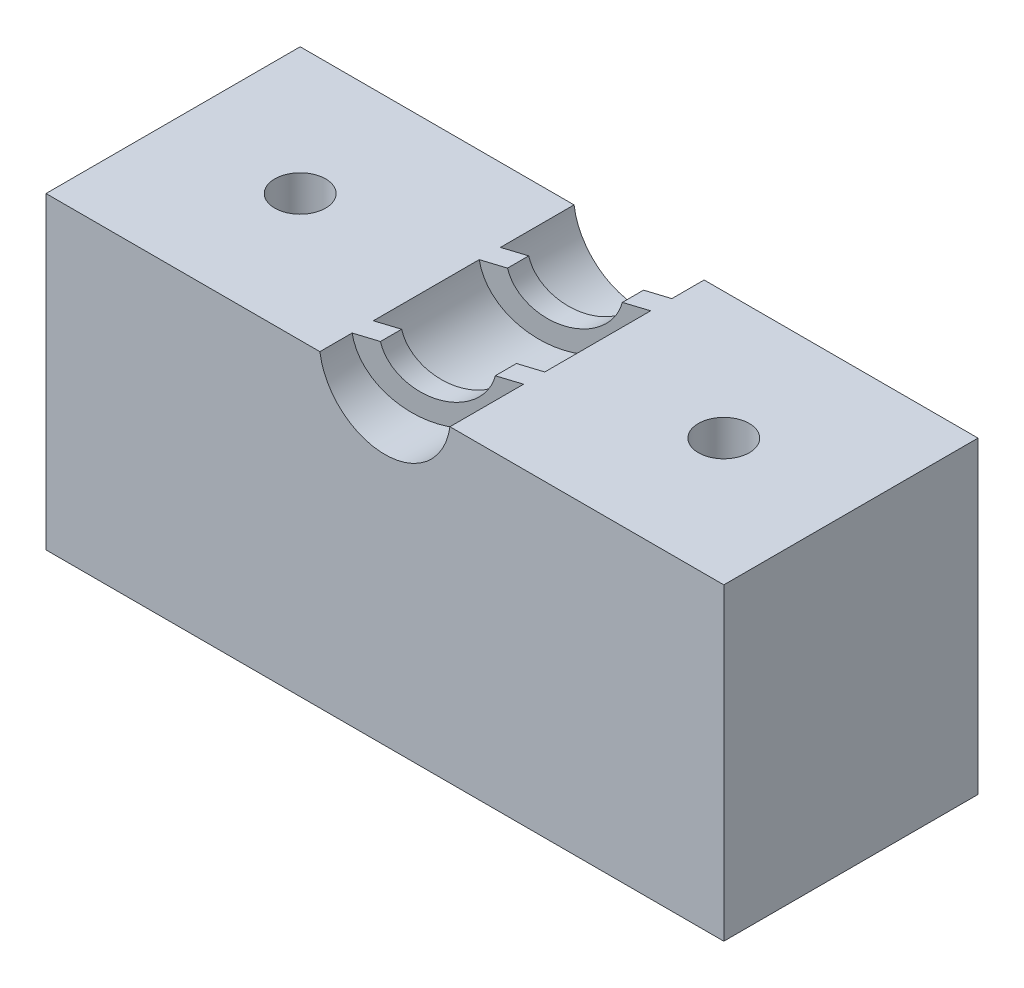
SolidWorks part; units mm, degrees
ref_plane "前视基准面" through (0, 0, 0) normal (0, 0, 1) x (1, 0, 0)
ref_plane "上视基准面" through (0, 0, 0) normal (0, 1, 0) x (1, 0, 0)
ref_plane "右视基准面" through (0, 0, 0) normal (1, 0, 0) x (0, 0, -1)
other "Configuration Table"
sketch "草图1" plane through (0, 0, 0) normal (0, 0, 1) x (1, 0, 0)
  line L1 (-8, -8) -> (8, -8)
  line L2 (-8, -8) -> (-8, 8)
  line L3 (-8, 8) -> (8, 8)
  line L4 (8, -8) -> (8, 8)
  line L5 (-8, -8) -> (8, 8) construction
  line L6 (-8, 8) -> (8, -8) construction
  circle A0 centre (0, 0) radius 1.55
  point P0 (0, 0)
  dimension "D3" = 3.1
  dimension "D1" = 16
  dimension "D2" = 16
extrude "凸台-拉伸1" add sketch "草图1" along normal mid plane 6
sketch "草图6" plane through (0, 0, 0) normal (0, 1, 0) x (1, 0, 0)
  line L0 (-1.55, -3) -> (1.55, -3) construction
  line L1 (1.55, 3) -> (-1.55, 3) construction
  line L2 (-1.55, -3) -> (1.55, -3)
  line L3 (1.55, 3) -> (-1.55, 3)
  line L4 (-1.55, 3) -> (-1.55, -3)
  line L5 (1.55, -3) -> (1.55, 3)
  line L6 (-1.55, 0.7565) -> (1.55, 1.7435)
  line L7 (1.55, 1.7435) -> (1.55, 2.2435)
  line L8 (1.55, 2.2435) -> (-1.55, 1.2565)
  line L9 (-1.55, -1.7435) -> (1.55, -0.7565)
  line L10 (-1.55, -2.2435) -> (1.55, -1.2565)
  line L11 (-2.0945, -0.6668) -> (3.135, 0.9981) construction
  line L12 (-3.1004, 0) -> (4.2723, 0) construction
  dimension "D1" = 2.5
  dimension "D2" = 0.5
  dimension "D3" = 0.5
  dimension "D4" = 17.66
extrude "凸台-拉伸2" add sketch "草图6" against normal up to surface (8 mm away) contours L4 L10 L5 L9 | L5 L8 L4 L6 region at (0, 0, 1.5) region at (0, 0, -1.5) up to face at (0, -8, 0)
sketch "草图7" plane through (0, 0, 0) normal (0, 0, 1) x (1, 0, 0)
  line L0 (0, 0) -> (-1.0279, -0.2141)
  line L1 (0, 0) -> (1.0279, -0.2141)
  line L2 (-1.0279, -0.2141) -> (-8, -0.2141)
  line L3 (1.0279, -0.2141) -> (8, -0.2141)
  line L6 (8, -8) -> (8, 8)
  line L7 (-8, -8) -> (8, -8)
  line L8 (-8, 8) -> (-8, -8)
  line L9 (8, 8) -> (-8, 8)
  line L10 (8, -8) -> (8, 8)
  line L11 (-8, -8) -> (8, -8)
  line L12 (-8, 8) -> (-8, -8)
  line L13 (8, 8) -> (-8, 8)
  circle A0 centre (0, 0) radius 1.05
  dimension "D1" = 2.1
  dimension "D2" = 0
  dimension "D3" = 156.47
extrude "切除-拉伸2" cut sketch "草图7" against normal through all both and the other way through all contours A0 L3 L10 L13 L12 L2 | L1 A0 L0 | L0 A0 L1 region at (0, -0.5019, 0) region at (0, 0.3858, 0) region at (0, 3.953, 0)
sketch "草图8" plane through (0, 0, 0) normal (0, 1, 0) x (1, 0, 0)
  line L0 (0, 5.5834) -> (0, -5.0797) construction
  circle A0 centre (-5, 0) radius 0.6
  circle A1 centre (5, 0) radius 0.6
  dimension "D2" = 1.2
  dimension "D3" = 10
extrude "切除-拉伸3" cut sketch "草图8" against normal through all
sketch "草图9" plane through (0, -8, 0) normal (0, -1, 0) x (1, 0, 0)
  line L4 (-8, -3) -> (8, -3)
  line L5 (8, -3) -> (8, 3)
  line L6 (8, 3) -> (-8, 3)
  line L7 (-8, 3) -> (-8, -3)
  line L8 (-8, -3) -> (8, -3)
  line L9 (8, -3) -> (8, 3)
  line L10 (8, 3) -> (-8, 3)
  line L11 (-8, 3) -> (-8, -3)
  dimension "D1" = 0
extrude "切除-拉伸4" cut sketch "草图9" against normal blind 0.5
equation "\"x\"=0.8094"
